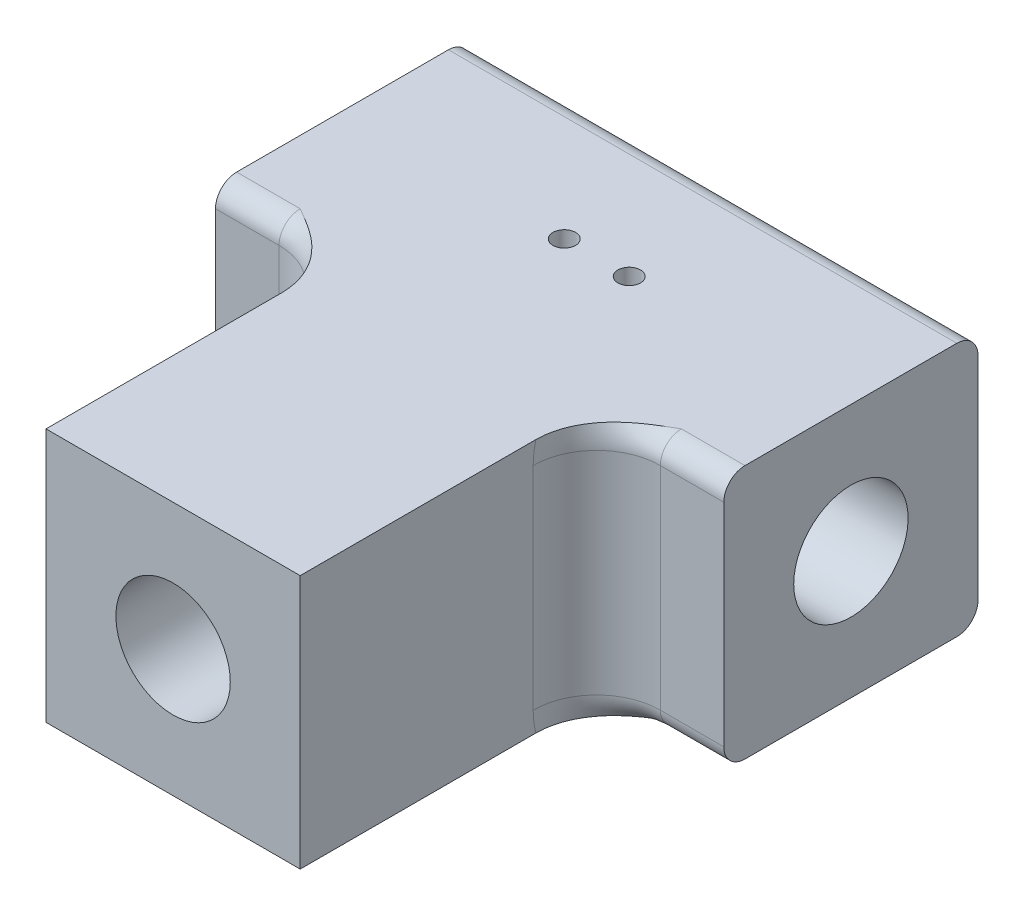
SolidWorks part; units mm, degrees
ref_plane "Front Plane" through (0, 0, 0) normal (0, 0, 1) x (1, 0, 0)
ref_plane "Top Plane" through (0, 0, 0) normal (0, 1, 0) x (1, 0, 0)
ref_plane "Right Plane" through (0, 0, 0) normal (1, 0, 0) x (0, 0, -1)
sketch "Sketch1" plane through (0, 0, 0) normal (0, 1, 0) x (1, 0, 0)
  line L3 (-6, -3) -> (6, -3)
  line L4 (-6, -3) -> (-6, 3)
  line L5 (-6, 3) -> (6, 3)
  line L6 (6, -3) -> (6, 3)
  line L7 (-6, -3) -> (6, 3) construction
  line L8 (-6, 3) -> (6, -3) construction
  point P0 (0, 0)
  dimension "D1" = 12
  dimension "D2" = 6
extrude "Boss-Extrude1" add sketch "Sketch1" along normal blind 6
sketch "Sketch2" plane through (0, 6, 0) normal (0, 1, 0) x (1, 0, 0)
  line L0 (-3.3, 0) -> (3.3, 0) construction
  point P0 (0.7667, 0)
  point P1 (-0.7667, 0)
  dimension "D1" = 1.5334
  dimension "D2" = 0.7667
sketch "Sketch6" plane through (-6, 0, 0) normal (-1, 0, 0) x (0, 0, 1)
  line L0 (0, -55) -> (0, 55) construction
  line L1 (-3, 6) -> (3, 6) construction
  point P0 (0, 4.5)
  dimension "D1" = 1.5
hole_wizard "#75 (0.021) Diameter Hole1" positions "Sketch9" profile "Sketch10" hole size "#75" standard "ANSI Inch" end condition through all
sketch "Sketch9" plane through (0, 6, 0) normal (0, 1, 0) x (1, 0, 0)
  point P0 (0.7667, 0)
  point P3 (-0.7667, 0)
sketch "Sketch10" plane through (0.7667, 6, 0) normal (1, 0, 0) x (0, 0, 1)
  line L0 (0, 0) -> (0, 6)
  line L1 (0, 6) -> (0.2667, 6)
  line L2 (0.2667, 6) -> (0.2667, 0)
  line L5 (0.2667, 0) -> (0, 0)
  line L11 (0, -6.35) -> (0, 107.95) construction
  dimension "Thru Hole Dia." = 0.5334
  dimension "Thru Hole Depth" = 6
hole_wizard "Tap Drill for M2x0.4 Tap1" [suppressed] positions "Sketch7" profile "Sketch8" hole size "M2x0.4" standard "ANSI Metric"
sketch "Sketch7" [suppressed] plane through (-5, 0, 0) normal (-1, 0, 0) x (0, 0, 1)
  point P0 (0, 1.5)
sketch "Sketch8" [suppressed] plane through (-5, 1.5, 0) normal (0, 1, 0) x (0, 0, 1)
  line L0 (0, 0) -> (0, 4.85)
  line L1 (0, 4.85) -> (0.8, 4.3693)
  line L2 (0.8, 4.3693) -> (0.8, 0)
  line L5 (0.8, 0) -> (0, 0)
  line L10 (0, 4.85) -> (-0.8, 4.3693) construction
  line L11 (0, -6.35) -> (0, 107.95) construction
  dimension "Hole Dia." = 1.6
  dimension "Hole Depth" = 4.85
  dimension "Drill Angle" = 118
mirror "Mirror1" [suppressed] about plane through (0, 0, 0) normal (1, 0, 0)
sketch "Sketch15" plane through (0, 0, 3) normal (0, 0, 1) x (1, 0, 0)
  line L0 (0, -3.3) -> (0, 3.3) construction
  line L1 (-3, 0) -> (3, 0)
  line L2 (-3, 0) -> (-3, 6)
  line L3 (-3, 6) -> (3, 6)
  line L4 (3, 0) -> (3, 6)
  line L5 (-3, 0) -> (3, 6) construction
  line L6 (-3, 6) -> (3, 0) construction
  line L7 (-6, 6) -> (6, 6) construction
  point P0 (0, 3)
  dimension "D1" = 6
  dimension "D2" = 6
extrude "Boss-Extrude2" add sketch "Sketch15" along normal blind 7
sketch "Sketch16" plane through (0, 0, 10) normal (0, 0, 1) x (1, 0, 0)
  line L0 (0, -3.3) -> (0, 3.3) construction
  line L1 (3, 6) -> (-3, 6) construction
  circle A0 centre (0, 3) radius 1.35
  point P0 (0, 3)
  dimension "D2" = 2.7
  dimension "D1" = 3
hole_wizard "M2x0.4 Tapped Hole1" [suppressed] positions "Sketch17" profile "Sketch18" tap size "M2x0.4" standard "ANSI Metric"
sketch "Sketch17" [suppressed] plane through (0, 0, 8.5) normal (0, 0, 1) x (1, 0, 0)
  point P0 (0, 1.5)
sketch "Sketch18" [suppressed] plane through (0, 1.5, 8.5) normal (1, 0, 0) x (0, -1, 0)
  line L0 (0, 0) -> (0, 5.4807)
  line L1 (0, 5.4807) -> (0.8, 5)
  line L2 (0.8, 5) -> (0.8, 0)
  line L5 (0.8, 0) -> (0, 0)
  line L10 (0, 5.4807) -> (-0.8, 5) construction
  line L11 (0, -6.35) -> (0, 107.95) construction
  dimension "Tap Drill Dia." = 1.6
  dimension "Tap Drill Depth" = 5
  dimension "Drill Angle" = 118
cosmetic thread "Hole Thread1" [suppressed] parameters "D1"=4, "D2"=2
fillet "Fillet4" radius 0.5 6 edges at (4.5, 6, 3) (4.5, 0, 3) (-4.5, 0, 3) (0, 0, -3) (0, 6, -3) (-4.5, 6, 3)
fillet "Fillet3" radius 1.5 6 edges at (-3, 3, 3) (3, 3, 3) (-3, 5.8536, 2.8536) (-3, 0.1464, 2.8536) (3, 0.1464, 2.8536) (3, 5.8536, 2.8536)
sketch "Sketch19" plane through (-6, 0, 0) normal (-1, 0, 0) x (0, 0, 1)
  line L0 (0, -3.3) -> (0, 3.3) construction
  line L1 (-2.5, 6) -> (2.5, 6) construction
  circle A0 centre (0, 3) radius 1.35
  dimension "D1" = 2.7
  dimension "D2" = 3
extrude "Cut-Extrude1" cut sketch "Sketch19" against normal blind 5.5 contours A0
extrude "Cut-Extrude2" cut sketch "Sketch16" against normal blind 5 contours A0
mirror "Mirror2" about plane through (0, 0, 0) normal (1, 0, 0) of "Cut-Extrude1"
